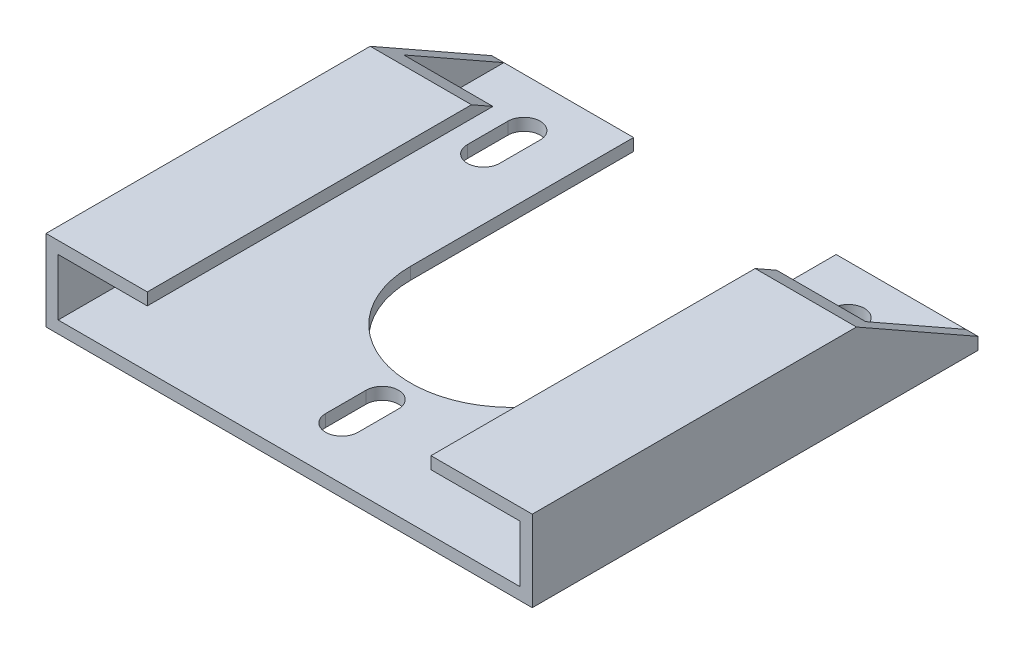
SolidWorks part; units mm, degrees
ref_plane "Front Plane" through (0, 0, 0) normal (0, 0, 1) x (1, 0, 0)
ref_plane "Top Plane" through (0, 0, 0) normal (0, 1, 0) x (1, 0, 0)
ref_plane "Right Plane" through (0, 0, 0) normal (1, 0, 0) x (0, 0, -1)
sketch "Sketch1" plane through (0, 0, 0) normal (0, 1, 0) x (1, 0, 0)
  line L0 (-57, 55) -> (-57, -55)
  line L1 (-60, 55) -> (-25, 55)
  line L2 (-60, 55) -> (-60, -55)
  line L3 (-60, -55) -> (60, -55)
  line L4 (60, 55) -> (60, -55)
  line L5 (-60, 55) -> (-57, 52.25) construction
  line L6 (-60, -55) -> (-57, -52.25) construction
  line L7 (57, 55) -> (57, -55)
  line L8 (-25, 0) -> (-25, 55)
  line L9 (25, 0) -> (25, 55)
  line L10 (25, 55) -> (60, 55)
  line L11 (57, -52.25) -> (60, -55) construction
  line L12 (57, 52.25) -> (60, 55) construction
  arc A0 (-25, 0) -> (25, 0) centre (0, 0) ccw
  point P0 (0, 0)
  dimension "D5" = 50
  dimension "D1" = 110
  dimension "D2" = 120
  dimension "D3" = 3
  dimension "D4" = 3
extrude "Boss-Extrude1" add sketch "Sketch1" along normal blind 3 contours A0 L8 L1 L0 L3 L7 L10 L9 region at (-41, 0, -53.4158)
extrude "Boss-Extrude2" add sketch "Sketch1<3>" along normal blind 20 contours L2 L3 L0 L1 | L10 L7 L3 L4 region at (-58.5, 0, 0) region at (58.5, 0, 0)
sketch "Sketch1<3>" plane through (0, 0, 0) normal (0, 1, 0) x (1, 0, 0) same geometry as "Sketch1"
sketch "Sketch4" plane through (-57, 0, 0) normal (1, 0, 0) x (0, 0, -1)
  line L1 (-55, 20) -> (-55, 17)
  line L2 (55, 17) -> (-55, 17)
  line L3 (55, 17) -> (-55, 17)
  line L4 (55, 20) -> (55, 17)
  line L5 (-55, 20) -> (55, 20)
  dimension "D1" = 3
extrude "Boss-Extrude3" add sketch "Sketch4" along normal blind 22
mirror "Mirror1" about plane through (0, 0, 0) normal (1, 0, 0) of "Boss-Extrude3"
sketch "Sketch5" plane through (0, 20, 0) normal (0, 1, 0) x (1, 0, 0)
  line L0 (-60, 25) -> (-35, 25) construction
  line L1 (-60, 55) -> (-60, -55) construction
  line L2 (-35, 55) -> (-35, -55) construction
  line L4 (-60, -55) -> (-35, -55) construction
  dimension "D1" = 80
ref_plane "Plane1" through (0, 25.8621, -14.6552) normal (0, 0.87, -0.493) x (1, 0, 0)
sketch "Sketch9" plane through (0, 25.8621, -14.6552) normal (0, 0.87, -0.493) x (1, 0, 0)
  line L1 (-79.8216, 63.565) -> (73.9527, 63.565)
  line L2 (-79.8216, 63.565) -> (-79.8216, 0)
  line L3 (-79.8216, 0) -> (73.9527, 0)
  line L4 (73.9527, 63.565) -> (73.9527, 0)
  line L5 (-79.8216, 63.565) -> (73.9527, 0) construction
  line L6 (-79.8216, 0) -> (73.9527, 63.565) construction
  point P0 (-2.9345, 31.7825)
extrude "Cut-Extrude1" cut sketch "Sketch9" along normal through all
sketch "Sketch10" plane through (0, 3, 0) normal (0, 1, 0) x (1, 0, 0)
  line L0 (-40, 42.9742) -> (-40, 32.9742) construction
  line L1 (-36, 42.9742) -> (-36, 32.9742)
  line L2 (-44, 42.9742) -> (-44, 32.9742)
  line L3 (-40, 46.9742) -> (-40, 28.9742) construction
  line L4 (-25, 0) -> (-25, 55) construction
  arc A0 (-36, 42.9742) -> (-44, 42.9742) centre (-40, 42.9742) ccw
  arc A1 (-44, 32.9742) -> (-36, 32.9742) centre (-40, 32.9742) ccw
  point P2 (-40, 37.9742)
  dimension "D1" = 8
  dimension "D2" = 18
  dimension "D3" = 15
extrude "Cut-Extrude2" cut sketch "Sketch10" against normal blind 22
mirror "Mirror2" about plane through (0, 0, 0) normal (1, 0, 0) of "Cut-Extrude2"
sketch "Sketch11" plane through (0, 3, 0) normal (0, 1, 0) x (1, 0, 0)
  line L0 (0, -32) -> (0, -42) construction
  line L1 (4, -32) -> (4, -42)
  line L2 (-4, -32) -> (-4, -42)
  line L3 (0, -28) -> (0, -46) construction
  line L4 (0, -25) -> (0, -55) construction
  line L5 (-57, -55) -> (57, -55) construction
  arc A0 (4, -32) -> (-4, -32) centre (0, -32) ccw
  arc A1 (-4, -42) -> (4, -42) centre (0, -42) ccw
  arc A2 (-25, 0) -> (25, 0) centre (0, 0) ccw construction
  point P2 (0, -37)
  point P16 (0, -40)
  dimension "D1" = 18
  dimension "D2" = 8
  dimension "D3" = 3
extrude "Cut-Extrude3" cut sketch "Sketch11" against normal blind 22
